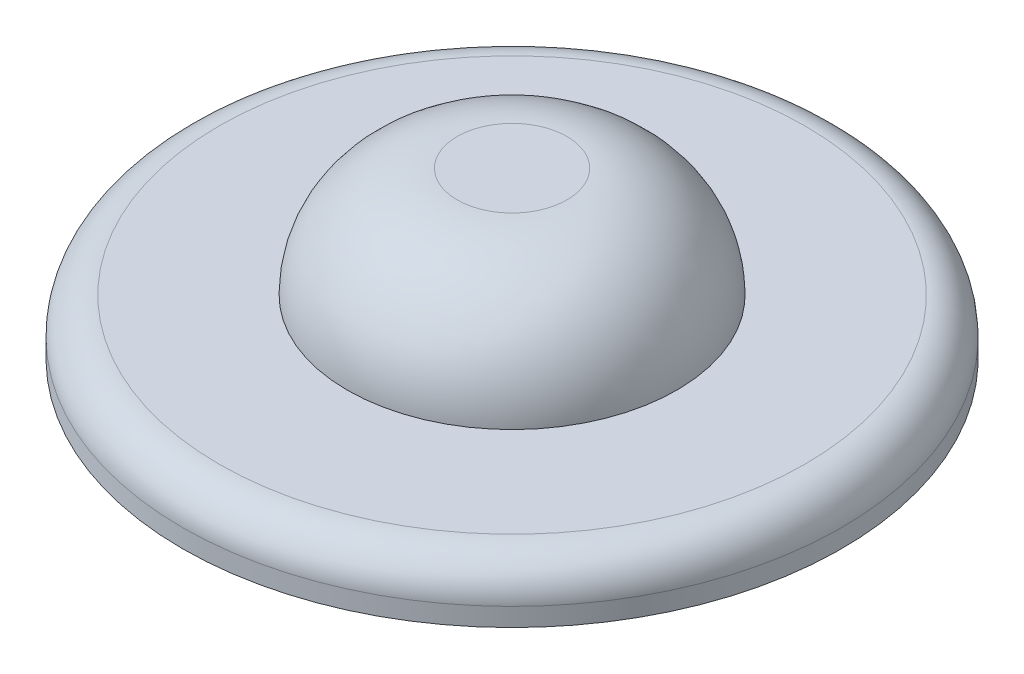
SolidWorks part; units mm, degrees
material "Custom Plastic"
ref_plane "Front Plane" through (0, 0, 0) normal (0, 0, 1) x (1, 0, 0)
ref_plane "Top Plane" through (0, 0, 0) normal (0, 1, 0) x (1, 0, 0)
ref_plane "Right Plane" through (0, 0, 0) normal (1, 0, 0) x (0, 0, -1)
sketch "Sketch1" plane through (0, 0, 0) normal (0, 1, 0) x (1, 0, 0)
  circle A0 centre (0, 0) radius 60
  dimension "D1" = 120
extrude "Boss-Extrude1" add sketch "Sketch1" along normal blind 10
sketch "Sketch2" plane through (0, 10, 0) normal (0, 1, 0) x (1, 0, 0)
  circle A0 centre (0, 0) radius 90
  dimension "D1" = 180
extrude "Boss-Extrude2" add sketch "Sketch2" along normal blind 15
sketch "Sketch3" plane through (0, 25, 0) normal (0, 1, 0) x (1, 0, 0)
  circle A0 centre (0, 0) radius 45
  dimension "D1" = 90
extrude "Boss-Extrude3" add sketch "Sketch3" along normal blind 30
fillet "Fillet1" radius 10 1 edges at (0, 25, 90)
fillet "Fillet2" radius 30 1 edges at (0, 55, 45)
